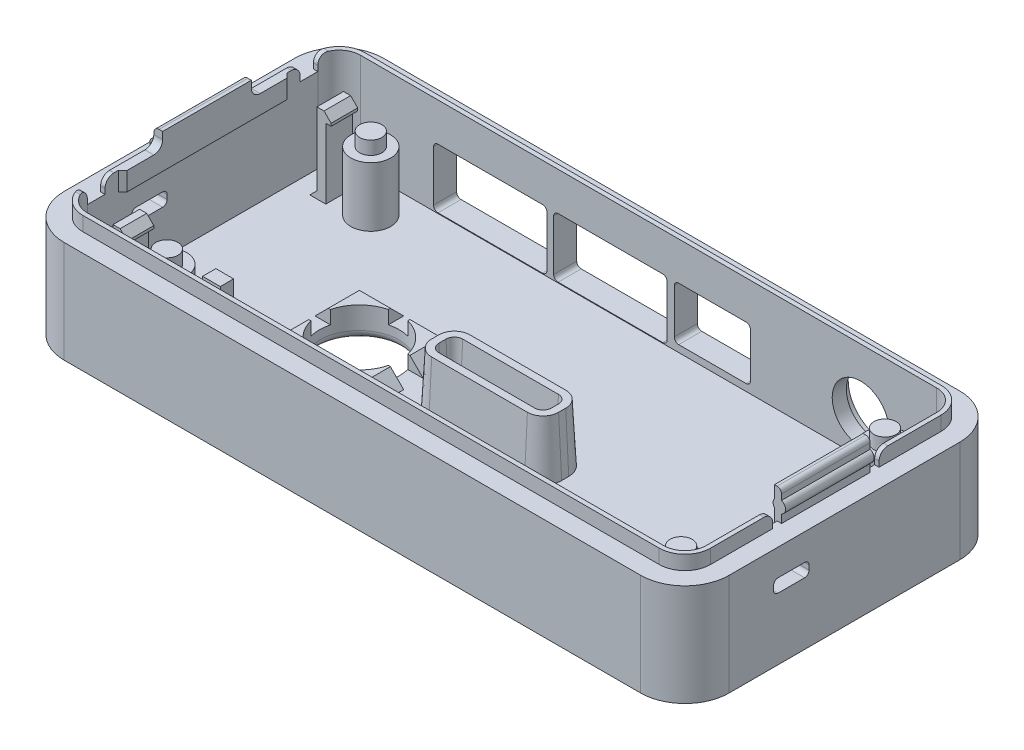
SolidWorks part; units mm, degrees
ref_plane "前视基准面" through (0, 0, 0) normal (0, 0, 1) x (1, 0, 0)
ref_plane "上视基准面" through (0, 0, 0) normal (0, 1, 0) x (1, 0, 0)
ref_plane "右视基准面" through (0, 0, 0) normal (1, 0, 0) x (0, 0, -1)
sketch "zero" plane through (0, 0, 0) normal (0, 1, 0) x (1, 0, 0)
  line L1 (-29.5, 15) -> (29.5, 15)
  line L2 (-32.5, 12) -> (-32.5, -12)
  line L3 (-29.5, -15) -> (29.5, -15)
  line L4 (32.5, 12) -> (32.5, -12)
  line L5 (-32.5, 15) -> (32.5, -15) construction
  line L6 (-32.5, -15) -> (32.5, 15) construction
  line L7 (-25.7, -15) -> (-14.5, -15)
  line L8 (-25.7, -15) -> (-25.7, -9.6569)
  line L9 (-25.7, -9.6569) -> (-14.5, -9.6569)
  line L10 (-14.5, -15) -> (-14.5, -9.6569)
  line L11 (5.2, -15) -> (12.7, -15)
  line L12 (5.2, -15) -> (5.2, -11)
  line L13 (5.2, -11) -> (12.7, -11)
  line L14 (12.7, -15) -> (12.7, -11)
  line L15 (17.8, -15) -> (25.3, -15)
  line L16 (17.8, -15) -> (17.8, -11)
  line L17 (17.8, -11) -> (25.3, -11)
  line L18 (25.3, -15) -> (25.3, -11)
  line L19 (-32.5, 7.7) -> (-19.5, 7.7)
  line L20 (-32.5, 7.7) -> (-32.5, -4.3)
  line L21 (-32.5, -4.3) -> (-19.5, -4.3)
  line L22 (-19.5, 7.7) -> (-19.5, -4.3)
  line L23 (-25.5, 14) -> (25.5, 14)
  line L24 (-25.5, 14) -> (-25.5, 8.8)
  line L25 (-25.5, 8.8) -> (25.5, 8.8)
  line L26 (25.5, 14) -> (25.5, 8.8)
  line L27 (-19.5, 7.2329) -> (-35.5, 7.2329)
  line L28 (-19.5, 7.2329) -> (-19.5, -3.7671)
  line L29 (-19.5, -3.7671) -> (-35.5, -3.7671)
  line L30 (-35.5, 7.2329) -> (-35.5, -3.7671)
  arc A0 (29.5, -15) -> (32.5, -12) centre (29.5, -12) ccw
  arc A1 (29.5, 15) -> (32.5, 12) centre (29.5, 12) cw
  arc A2 (-32.5, -12) -> (-29.5, -15) centre (-29.5, -12) ccw
  arc A3 (-29.5, 15) -> (-32.5, 12) centre (-29.5, 12) ccw
  circle A4 centre (-29, 11.4) radius 3
  circle A5 centre (-29, -11.5) radius 3
  circle A6 centre (29, 11.4) radius 3
  circle A7 centre (29, -11.5) radius 3
  circle A8 centre (-29, 11.4) radius 1.375
  circle A9 centre (-29, -11.5) radius 1.375
  circle A10 centre (29, -11.5) radius 1.375
  circle A11 centre (29, 11.4) radius 1.375
  point P0 (0, 0)
  dimension "D3" = 3
  dimension "D4" = 6
  dimension "D9" = 2.75
  dimension "D1" = 65
  dimension "D2" = 30
  dimension "D5" = 3.6
  dimension "D6" = 3.5
  dimension "D7" = 3.5
  dimension "D8" = 3.5
  dimension "D10" = 12
  dimension "D11" = 7.3
  dimension "D12" = 13
  dimension "D13" = 11.2
  dimension "D14" = 6.8
  dimension "D15" = 19.7
  dimension "D16" = 7.5
  dimension "D17" = 7.5
  dimension "D18" = 5.1
  dimension "D19" = 4
  dimension "D20" = 5.2
  dimension "D21" = 7
  dimension "D22" = 7
  dimension "D23" = 1
  dimension "D24" = 11
  dimension "D25" = 16
sketch "sugar" plane through (0, 0, 0) normal (0, 1, 0) x (1, 0, 0)
  line L1 (-29.5, 15) -> (29.5, 15)
  line L2 (-32.5, 12) -> (-32.5, -12)
  line L3 (-29.5, -15) -> (29.5, -15)
  line L4 (32.5, 12) -> (32.5, -12)
  line L5 (-32.5, 15) -> (32.5, -15) construction
  line L6 (-32.5, -15) -> (32.5, 15) construction
  line L7 (23.5, -11.5) -> (19.5, -11.5)
  line L8 (23.5, -11.5) -> (23.5, -13.9082)
  line L9 (23.5, -13.9082) -> (19.5, -13.9082)
  line L10 (19.5, -11.5) -> (19.5, -13.9082)
  line L11 (16, -11.0071) -> (8.5, -11.0071)
  line L12 (16, -11.0071) -> (16, -15)
  line L13 (16, -15) -> (8.5, -15)
  line L14 (8.5, -11.0071) -> (8.5, -15)
  line L15 (20.5, -13.9082) -> (22.5, -13.9082)
  line L16 (20.5, -13.9082) -> (20.5, -14.8173)
  line L17 (20.5, -14.8173) -> (22.5, -14.8173)
  line L18 (22.5, -13.9082) -> (22.5, -14.8173)
  arc A0 (29.5, 15) -> (32.5, 12) centre (29.5, 12) cw
  arc A1 (29.5, -15) -> (32.5, -12) centre (29.5, -12) ccw
  arc A2 (-32.5, -12) -> (-29.5, -15) centre (-29.5, -12) ccw
  arc A3 (-29.5, 15) -> (-32.5, 12) centre (-29.5, 12) ccw
  circle A4 centre (-29, 11.4) radius 3
  circle A5 centre (-29, 11.4) radius 1.375
  circle A6 centre (-29, -11.5) radius 3
  circle A7 centre (-29, -11.5) radius 1.375
  circle A8 centre (29, 11.4) radius 3
  circle A9 centre (29, 11.4) radius 1.375
  circle A10 centre (29, -11.5) radius 3
  circle A11 centre (29, -11.5) radius 1.375
  dimension "D3" = 3
  dimension "D1" = 65
  dimension "D2" = 30
  dimension "D4" = 9
  dimension "D5" = 4
  dimension "D6" = 3.5
  dimension "D7" = 7.5
  dimension "D8" = 2
  dimension "D9" = 1
sketch "case" plane through (0, 0, 0) normal (0, 1, 0) x (1, 0, 0)
  line L1 (-34.0422, 18) -> (30.9578, 18)
  line L2 (-39.0422, 13) -> (-39.0422, -13)
  line L3 (-34.0422, -18) -> (30.9578, -18)
  line L4 (35.9578, 13) -> (35.9578, -13)
  line L5 (-39.0422, 18) -> (35.9578, -18) construction
  line L6 (-39.0422, -18) -> (35.9578, 18) construction
  arc A0 (-39.0422, -13) -> (-34.0422, -18) centre (-34.0422, -13) ccw
  arc A1 (30.9578, -18) -> (35.9578, -13) centre (30.9578, -13) ccw
  arc A2 (30.9578, 18) -> (35.9578, 13) centre (30.9578, 13) cw
  arc A3 (-34.0422, 18) -> (-39.0422, 13) centre (-34.0422, 13) ccw
  point P0 (-1.5422, 0)
  point P3 (-1.5422, 0)
  dimension "D3" = 5
  dimension "D1" = 75
  dimension "D2" = 36
extrude "凸台-拉伸2" add sketch "case" along normal blind 11.5
sketch "草图2" plane through (0, 0, 0) normal (0, 1, 0) x (1, 0, 0)
  line L4 (-34.0422, -15.4) -> (30.9578, -15.4)
  line L5 (33.3578, -13) -> (33.3578, 13)
  line L6 (30.9578, 15.4) -> (-34.0422, 15.4)
  line L7 (-36.4422, 13) -> (-36.4422, -13)
  line L8 (33.8578, -13) -> (33.8578, 13)
  line L9 (30.9578, 15.9) -> (-34.0422, 15.9)
  line L10 (-36.9422, 13) -> (-36.9422, -13)
  line L11 (-34.0422, -15.9) -> (30.9578, -15.9)
  line L12 (33.8578, -13) -> (33.8578, 13)
  line L13 (30.9578, 15.9) -> (-34.0422, 15.9)
  line L14 (-36.9422, 13) -> (-36.9422, -13)
  line L15 (-34.0422, -15.9) -> (30.9578, -15.9)
  arc A4 (30.9578, -15.4) -> (33.3578, -13) centre (30.9578, -13) ccw
  arc A5 (33.3578, 13) -> (30.9578, 15.4) centre (30.9578, 13) ccw
  arc A6 (-34.0422, 15.4) -> (-36.4422, 13) centre (-34.0422, 13) ccw
  arc A7 (-36.4422, -13) -> (-34.0422, -15.4) centre (-34.0422, -13) ccw
  arc A8 (30.9578, -15.9) -> (33.8578, -13) centre (30.9578, -13) ccw
  arc A9 (33.8578, 13) -> (30.9578, 15.9) centre (30.9578, 13) ccw
  arc A10 (-34.0422, 15.9) -> (-36.9422, 13) centre (-34.0422, 13) ccw
  arc A11 (-36.9422, -13) -> (-34.0422, -15.9) centre (-34.0422, -13) ccw
  arc A12 (30.9578, -15.9) -> (33.8578, -13) centre (30.9578, -13) ccw
  arc A13 (33.8578, 13) -> (30.9578, 15.9) centre (30.9578, 13) ccw
  arc A14 (-34.0422, 15.9) -> (-36.9422, 13) centre (-34.0422, 13) ccw
  arc A15 (-36.9422, -13) -> (-34.0422, -15.9) centre (-34.0422, -13) ccw
  dimension "D1" = 2.1
  dimension "D2" = 0.5
ref_plane "基准面1" through (0, 11.5, 0) normal (0, 1, 0) x (1, 0, 0)
sketch "草图3" plane through (0, 11.5, 0) normal (0, 1, 0) x (1, 0, 0)
  line L4 (-34.0422, -15.4) -> (30.9578, -15.4)
  line L5 (33.3578, -13) -> (33.3578, 13)
  line L6 (30.9578, 15.4) -> (-34.0422, 15.4)
  line L7 (-36.4422, 13) -> (-36.4422, -13)
  line L8 (-34.0422, -15.4) -> (30.9578, -15.4)
  line L9 (33.3578, -13) -> (33.3578, 13)
  line L10 (30.9578, 15.4) -> (-34.0422, 15.4)
  line L11 (-36.4422, 13) -> (-36.4422, -13)
  line L12 (-36.9422, 13) -> (-36.9422, -13)
  line L13 (-34.0422, -15.9) -> (30.9578, -15.9)
  line L14 (33.8578, -13) -> (33.8578, 13)
  line L15 (30.9578, 15.9) -> (-34.0422, 15.9)
  line L16 (-36.9422, 13) -> (-36.9422, -13)
  line L17 (-34.0422, -15.9) -> (30.9578, -15.9)
  line L18 (33.8578, -13) -> (33.8578, 13)
  line L19 (30.9578, 15.9) -> (-34.0422, 15.9)
  arc A4 (30.9578, -15.4) -> (33.3578, -13) centre (30.9578, -13) ccw
  arc A5 (33.3578, 13) -> (30.9578, 15.4) centre (30.9578, 13) ccw
  arc A6 (-34.0422, 15.4) -> (-36.4422, 13) centre (-34.0422, 13) ccw
  arc A7 (-36.4422, -13) -> (-34.0422, -15.4) centre (-34.0422, -13) ccw
  arc A8 (30.9578, -15.4) -> (33.3578, -13) centre (30.9578, -13) ccw
  arc A9 (33.3578, 13) -> (30.9578, 15.4) centre (30.9578, 13) ccw
  arc A10 (-34.0422, 15.4) -> (-36.4422, 13) centre (-34.0422, 13) ccw
  arc A11 (-36.4422, -13) -> (-34.0422, -15.4) centre (-34.0422, -13) ccw
  arc A12 (-36.9422, -13) -> (-34.0422, -15.9) centre (-34.0422, -13) ccw
  arc A13 (30.9578, -15.9) -> (33.8578, -13) centre (30.9578, -13) ccw
  arc A14 (33.8578, 13) -> (30.9578, 15.9) centre (30.9578, 13) ccw
  arc A15 (-34.0422, 15.9) -> (-36.9422, 13) centre (-34.0422, 13) ccw
  arc A16 (-36.9422, -13) -> (-34.0422, -15.9) centre (-34.0422, -13) ccw
  arc A17 (30.9578, -15.9) -> (33.8578, -13) centre (30.9578, -13) ccw
  arc A18 (33.8578, 13) -> (30.9578, 15.9) centre (30.9578, 13) ccw
  arc A19 (-34.0422, 15.9) -> (-36.9422, 13) centre (-34.0422, 13) ccw
  dimension "D1" = 0
  dimension "D2" = 0
extrude "凸台-拉伸4" add sketch "草图3" along normal blind 1.6
sketch "草图5" plane through (0, 11.5, 0) normal (0, 1, 0) x (1, 0, 0)
  line L0 (33.3578, -13) -> (33.3578, 13) construction
  line L1 (33.0578, 5) -> (33.3578, 5)
  line L2 (33.0578, 5) -> (33.0578, -5)
  line L3 (33.0578, -5) -> (33.3578, -5)
  line L4 (33.3578, 5) -> (33.3578, -5)
  line L5 (33.0578, 5) -> (33.3578, -5) construction
  line L6 (33.0578, -5) -> (33.3578, 5) construction
  point P0 (33.2078, 0)
  dimension "D2" = 10
  dimension "D3" = 0.3
  dimension "D4" = 0
ref_plane "基准面3" through (33.8578, 0, 0) normal (1, 0, 0) x (0, 0, -1)
ref_plane "基准面7" through (-36.9422, 0, 0) normal (-1, 0, 0) x (0, 0, 1)
ref_plane "基准面8" through (0, 0, 0) normal (0, -1, 0) x (-1, 0, 0)
sketch "草图14" plane through (0, 11.5, 0) normal (0, 1, 0) x (1, 0, 0)
  line L4 (-34.0422, -15.4) -> (30.9578, -15.4)
  line L5 (33.3578, -13) -> (33.3578, 13)
  line L6 (30.9578, 15.4) -> (-34.0422, 15.4)
  line L7 (-36.4422, 13) -> (-36.4422, -13)
  line L8 (-34.0422, -15.4) -> (30.9578, -15.4)
  line L9 (33.3578, -13) -> (33.3578, 13)
  line L10 (30.9578, 15.4) -> (-34.0422, 15.4)
  line L11 (-36.4422, 13) -> (-36.4422, -13)
  arc A4 (30.9578, -15.4) -> (33.3578, -13) centre (30.9578, -13) ccw
  arc A5 (33.3578, 13) -> (30.9578, 15.4) centre (30.9578, 13) ccw
  arc A6 (-34.0422, 15.4) -> (-36.4422, 13) centre (-34.0422, 13) ccw
  arc A7 (-36.4422, -13) -> (-34.0422, -15.4) centre (-34.0422, -13) ccw
  arc A8 (30.9578, -15.4) -> (33.3578, -13) centre (30.9578, -13) ccw
  arc A9 (33.3578, 13) -> (30.9578, 15.4) centre (30.9578, 13) ccw
  arc A10 (-34.0422, 15.4) -> (-36.4422, 13) centre (-34.0422, 13) ccw
  arc A11 (-36.4422, -13) -> (-34.0422, -15.4) centre (-34.0422, -13) ccw
  dimension "D1" = 0
extrude "切除-拉伸2" cut sketch "草图14" against normal blind 9.5
extrude "凸台-拉伸12" add sketch "草图5" against normal blind 2 and the other way blind 1.6
sketch "草图15" plane through (0, 2, 0) normal (0, 1, 0) x (1, 0, 0)
  line L1 (35.9578, -13) -> (35.9578, 13) construction
  line L5 (-39.0422, 13) -> (-39.0422, -13) construction
  line L6 (-34.0422, -18) -> (30.9578, -18) construction
  line L7 (30.9578, 18) -> (-34.0422, 18) construction
  circle A0 centre (29.0603, -11.5295) radius 2.25
  circle A1 centre (-28.9397, -11.5295) radius 2.25
  circle A2 centre (29.0603, 11.4705) radius 2.25
  circle A3 centre (-28.9397, 11.4705) radius 2.25
  dimension "D1" = 4.5
  dimension "D2" = 6.8975
  dimension "D3" = 10.1025
  dimension "D4" = 6.4705
  dimension "D5" = 6.5295
extrude "凸台-拉伸13" add sketch "草图15" along normal blind 6.7
sketch "草图16" plane through (0, 8.7, 0) normal (0, 1, 0) x (1, 0, 0)
  circle A0 centre (29.0603, -11.5295) radius 1.25
  circle A1 centre (29.0603, 11.4705) radius 1.25
  circle A2 centre (-28.9397, -11.5295) radius 1.25
  circle A3 centre (-28.9397, 11.4705) radius 1.25
  dimension "D1" = 2.5
extrude "凸台-拉伸14" add sketch "草图16" along normal blind 1.5
sketch "草图17" plane through (0, 13.1, 0) normal (0, 1, 0) x (1, 0, 0)
  line L0 (33.3578, -13) -> (33.3578, -5) construction
  line L1 (33.3578, -5) -> (33.8578, -5)
  line L2 (33.3578, -5) -> (33.3578, -6)
  line L3 (33.3578, -6) -> (33.8578, -6)
  line L4 (33.8578, -5) -> (33.8578, -6)
  line L5 (33.3578, -13) -> (33.3578, 13) construction
  line L6 (33.8578, -13) -> (33.8578, 13) construction
  line L8 (33.3578, 5) -> (33.8578, 5)
  line L9 (33.3578, 5) -> (33.3578, 6)
  line L10 (33.3578, 6) -> (33.8578, 6)
  line L11 (33.8578, 5) -> (33.8578, 6)
  dimension "D1" = 1
  dimension "D2" = 1
extrude "切除-拉伸3" cut sketch "草图17" against normal blind 1.6
sketch "草图19" plane through (0, 13.1, 0) normal (0, 1, 0) x (1, 0, 0)
  line L0 (33.0578, 5) -> (33.0578, -5) construction
  line L1 (33.8578, -5) -> (33.0578, -5)
  line L2 (33.8578, -5) -> (33.8578, 5)
  line L3 (33.8578, 5) -> (33.0578, 5)
  line L4 (33.0578, -5) -> (33.0578, 5)
extrude "凸台-拉伸15" add sketch "草图19" along normal blind 1.8
sketch "草图20" plane through (0, 0, -5) normal (0, 0, -1) x (-1, 0, 0)
  line L0 (-30.9578, 11.5) -> (-35.9578, 11.5) construction
  line L3 (-33.8578, 11.5) -> (-33.8578, 14.9) construction
  circle A0 centre (-33.6078, 13.1) radius 0.7
  dimension "D1" = 1.4
  dimension "D2" = 1.6
  dimension "D3" = 0.25
extrude "凸台-拉伸16" add sketch "草图20" against normal blind 10
fillet "圆角4" radius 0.5 1 edges at (33.8578, 14.9, 0)
sketch "草图39" plane through (0, 0, -18) normal (0, 0, -1) x (-1, 0, 0)
  line L0 (-30.9578, 0) -> (34.0422, 0) construction
  line L1 (-35.9578, 11.5) -> (-35.9578, 0) construction
  circle A0 centre (-22.3721, 6.2789) radius 4
  dimension "D1" = 6.2789
  dimension "D3" = 8
  dimension "D2" = 13.5857
extrude "切除-拉伸4" cut sketch "草图39" against normal blind 1
sketch "草图41" plane through (0, 0, -18) normal (0, 0, -1) x (-1, 0, 0)
  line L0 (-30.9578, 0) -> (34.0422, 0) construction
  line L1 (-9.9578, 2.7789) -> (-1.3578, 2.7789)
  line L2 (-9.9578, 2.7789) -> (-9.9578, 8.7789)
  line L3 (-9.9578, 8.7789) -> (-1.3578, 8.7789)
  line L4 (-1.3578, 2.7789) -> (-1.3578, 8.7789)
  line L5 (-0.5578, 2.0789) -> (12.2422, 2.0789)
  line L6 (-0.5578, 2.0789) -> (-0.5578, 8.7789)
  line L7 (-0.5578, 8.7789) -> (12.2422, 8.7789)
  line L8 (12.2422, 2.0789) -> (12.2422, 8.7789)
  line L9 (12.9922, 2.0789) -> (25.7922, 2.0789)
  line L10 (12.9922, 2.0789) -> (12.9922, 8.7789)
  line L11 (12.9922, 8.7789) -> (25.7922, 8.7789)
  line L12 (25.7922, 2.0789) -> (25.7922, 8.7789)
  line L13 (-35.9578, 11.5) -> (-35.9578, 0) construction
  dimension "D1" = 8.7789
  dimension "D2" = 26
  dimension "D3" = 8.6
  dimension "D4" = 6
  dimension "D5" = 0.8
  dimension "D6" = 6.7
  dimension "D7" = 12.8
  dimension "D8" = 0.75
  dimension "D9" = 12.8
extrude "切除-拉伸5" cut sketch "草图41" against normal blind 12
sketch "草图42" plane through (0, 0, -17) normal (0, 0, -1) x (-1, 0, 0)
  circle A0 centre (-22.3721, 6.2789) radius 3.2
  circle A1 centre (-22.3721, 6.2789) radius 4 construction
  point P2 (0, 0)
extrude "切除-拉伸6" cut sketch "草图42" against normal blind 1.6
sketch "草图46" plane through (-36.4422, 0, 0) normal (1, 0, 0) x (0, 0, -1)
  line L0 (13, 13.1) -> (-13, 13.1) construction
  line L1 (-10, 13.1) -> (10, 13.1)
  line L2 (-10, 13.1) -> (-10, 11)
  line L3 (-10, 11) -> (10, 11)
  line L4 (10, 13.1) -> (10, 11)
  line L6 (-18, 11.5) -> (-18, 0) construction
  dimension "D1" = 8
  dimension "D2" = 8
extrude "凸台-拉伸19" add sketch "草图46" along normal blind 0.5
chamfer "倒角3" distance 1 angle 45 2 edges at (-35.9422, 12.05, -10) (-35.9422, 12.05, 10)
sketch "草图48" plane through (0, 13.1, 0) normal (0, 1, 0) x (1, 0, 0)
  line L0 (-35.9422, 9) -> (-35.9422, -9) construction
  line L1 (-35.9422, -5) -> (-36.9422, -5)
  line L2 (-35.9422, -5) -> (-35.9422, 5)
  line L3 (-35.9422, 5) -> (-36.9422, 5)
  line L4 (-36.9422, -5) -> (-36.9422, 5)
  line L5 (-36.9422, 13) -> (-36.9422, -13) construction
extrude "凸台-拉伸21" add sketch "草图48" along normal blind 1.8
sketch "草图49" plane through (0, 0, 5) normal (0, 0, 1) x (1, 0, 0)
  line L0 (-34.0422, 11.5) -> (-39.0422, 11.5) construction
  line L1 (-36.9422, 14.9) -> (-36.9422, 13.1) construction
  circle A0 centre (-36.6922, 13.1) radius 0.7
  dimension "D1" = 1.4
  dimension "D2" = 1.6
  dimension "D3" = 0.25
extrude "凸台-拉伸22" add sketch "草图49" against normal blind 10
sketch "草图50" plane through (0, 13.1, 0) normal (0, 1, 0) x (1, 0, 0)
  line L0 (-36.4422, 13) -> (-36.4422, 9.5) construction
  line L1 (-36.4422, 13) -> (-36.9422, 13)
  line L2 (-36.4422, 13) -> (-36.4422, 11)
  line L3 (-36.4422, 11) -> (-36.9422, 11)
  line L4 (-36.9422, 13) -> (-36.9422, 11)
  line L5 (-36.9422, 13) -> (-36.9422, 5) construction
  line L6 (-36.4422, -9.5) -> (-36.4422, -13) construction
  line L7 (-36.4422, -11) -> (-36.9422, -11)
  line L8 (-36.4422, -11) -> (-36.4422, -13)
  line L9 (-36.4422, -13) -> (-36.9422, -13)
  line L10 (-36.9422, -11) -> (-36.9422, -13)
  line L11 (-36.9422, -5) -> (-36.9422, -13) construction
  line L12 (30.9578, 18) -> (-34.0422, 18) construction
  line L13 (-34.0422, -18) -> (30.9578, -18) construction
  dimension "D1" = 2
  dimension "D2" = 2
  dimension "D3" = 5
  dimension "D4" = 5
extrude "切除-拉伸10" cut sketch "草图50" against normal blind 1.6
fillet "圆角9" radius 1 6 edges at (33.6078, 13.1, 6) (33.6078, 13.1, -6) (-36.6922, 13.1, -13) (-36.6922, 13.1, -11) (-36.6922, 13.1, 11) (-36.6922, 13.1, 13)
fillet "圆角10" radius 0.6 1 edges at (-36.9422, 14.9, 0)
sketch "草图51" plane through (0, 0, 0) normal (0, -1, 0) x (1, 0, 0)
  line L0 (35.9578, 13) -> (35.9578, -13) construction
  line L1 (6.2578, 2.3) -> (-5.7422, 2.3)
  line L2 (6.2578, 2.3) -> (6.2578, 4.3)
  line L3 (6.2578, 4.3) -> (-5.7422, 4.3)
  line L4 (-5.7422, 2.3) -> (-5.7422, 4.3)
  line L5 (30.9578, -18) -> (-34.0422, -18) construction
  dimension "D1" = 2
  dimension "D2" = 12
  dimension "D3" = 29.7
  dimension "D4" = 20.3
extrude "切除-拉伸11" cut sketch "草图51" against normal blind 2
fillet "圆角13" radius 0.6 4 edges at (-5.7422, 1, 4.3) (-5.7422, 1, 2.3) (6.2578, 1, 4.3) (6.2578, 1, 2.3)
sketch "草图52" plane through (0, 2, 0) normal (0, 1, 0) x (1, 0, 0)
  line L0 (-11.5279, -7.2295) -> (-20.7279, -7.2295)
  line L5 (-20.7279, -7.2295) -> (-20.7279, 1.9705)
  line L6 (-11.5279, 1.9705) -> (-20.7279, 1.9705)
  line L7 (-11.5279, -7.2295) -> (-11.5279, 1.9705)
  line L8 (-39.0422, 13) -> (-39.0422, -13) construction
  line L9 (-34.0422, -18) -> (30.9578, -18) construction
  dimension "D1" = 9.2
  dimension "D2" = 9.2
  dimension "D3" = 18.3143
  dimension "D4" = 10.7705
extrude "凸台-拉伸23" add sketch "草图52" along normal blind 1.5
chamfer "倒角5" distance 1.5 angle 45 4 edges at (-16.1279, 2, -1.9705) (-11.5279, 2, 2.6295) (-16.1279, 2, 7.2295) (-20.7279, 2, 2.6295)
sketch "草图53" plane through (0, 0, 0) normal (0, -1, 0) x (1, 0, 0)
  line L1 (30.9578, -18) -> (-34.0422, -18) construction
  line L2 (-39.0422, -13) -> (-39.0422, 13) construction
  circle A0 centre (-16.1279, 2.6295) radius 4.5
  dimension "D1" = 9
  dimension "D2" = 20.6295
  dimension "D3" = 22.9143
extrude "切除-拉伸12" cut sketch "草图53" against normal up to next
fillet "圆角14" radius 1 1 edges at (-16.1279, 0, -1.8705)
sketch "草图55" plane through (0, 3.5, 0) normal (0, 1, 0) x (1, 0, 0)
  line L1 (-10.0279, -3.7295) -> (-22.2279, -3.7295)
  line L2 (-10.0279, -3.7295) -> (-10.0279, -1.5295)
  line L3 (-10.0279, -1.5295) -> (-22.2279, -1.5295)
  line L4 (-22.2279, -3.7295) -> (-22.2279, -1.5295)
  line L5 (-10.0279, -3.7295) -> (-22.2279, -1.5295) construction
  line L6 (-10.0279, -1.5295) -> (-22.2279, -3.7295) construction
  circle A0 centre (-16.1279, -2.6295) radius 4.5 construction
  point P0 (-16.1279, -2.6295)
  dimension "D1" = 12.2
  dimension "D2" = 2.2
extrude "切除-拉伸13" cut sketch "草图55" against normal blind 1.5
sketch "草图56" plane through (0, 3.5, 0) normal (0, 1, 0) x (1, 0, 0)
  line L1 (-15.0279, -8.7295) -> (-17.2279, -8.7295)
  line L2 (-15.0279, -8.7295) -> (-15.0279, 3.4705)
  line L3 (-15.0279, 3.4705) -> (-17.2279, 3.4705)
  line L4 (-17.2279, -8.7295) -> (-17.2279, 3.4705)
  line L5 (-15.0279, -8.7295) -> (-17.2279, 3.4705) construction
  line L6 (-15.0279, 3.4705) -> (-17.2279, -8.7295) construction
  arc A0 (-11.7644, -3.7295) -> (-11.7644, -1.5295) centre (-16.1279, -2.6295) ccw construction
  point P0 (-16.1279, -2.6295)
  dimension "D1" = 12.2
  dimension "D2" = 2.2
extrude "切除-拉伸14" cut sketch "草图56" against normal blind 1.5
sketch "草图62" plane through (0, 0, 0) normal (0, -1, 0) x (1, 0, 0)
  line L54 (31.3299, 13.3324) -> (30.9169, 13.5642)
  line L55 (30.9169, 13.5642) -> (28.7745, 14.7678)
  line L56 (28.7745, 14.7678) -> (28.3615, 15.0024)
  line L57 (27.5011, 14.9926) -> (27.0935, 14.7486)
  line L58 (27.0935, 14.7486) -> (24.9793, 13.4962)
  line L60 (24.9793, 13.4962) -> (24.5717, 13.255)
  line L61 (24.15, 12.5065) -> (24.189, 9.0989)
  line L62 (24.6278, 8.3602) -> (25.0408, 8.1284)
  line L63 (25.0408, 8.1284) -> (27.1831, 6.9248)
  line L65 (27.1831, 6.9248) -> (27.5962, 6.6902)
  line L66 (28.4566, 6.7) -> (28.8641, 6.9441)
  line L67 (28.8641, 6.9441) -> (30.9784, 8.1964)
  line L68 (30.9784, 8.1964) -> (31.3859, 8.4376)
  line L69 (31.8076, 9.1861) -> (31.7686, 12.5937)
  line L70 (25.1226, 12.9222) -> (27.7378, 14.4738)
  line L73 (28.1396, 14.4784) -> (30.7754, 12.9841)
  line L74 (30.7822, 12.6337) -> (28.2554, 11.0831)
  line L75 (29.0741, 8.5137) -> (28.7797, 8.3451)
  line L76 (28.7517, 8.2963) -> (28.7615, 7.4416)
  line L77 (28.7336, 7.3928) -> (28.1845, 7.0731)
  line L78 (28.1013, 7.1205) -> (28.0711, 9.7589)
  line L79 (28.099, 9.8076) -> (29.0331, 10.3512)
  line L80 (31.0237, 8.7127) -> (30.4803, 8.3959)
  line L81 (30.3971, 8.4434) -> (30.3827, 9.6998)
  line L82 (30.4107, 9.7486) -> (30.9541, 10.0626)
  line L83 (31.0373, 10.0151) -> (31.0517, 8.7615)
  line L84 (29.0341, 9.0205) -> (28.7735, 8.8864)
  line L85 (28.7443, 8.9459) -> (28.7366, 9.6183)
  line L86 (28.7646, 9.6671) -> (29.008, 9.8066)
  line L129 (28.7735, 8.8864) -> (28.7797, 8.3451)
  line L130 (28.7443, 8.9459) -> (28.7517, 8.2963)
  spline S0 degree 3 poles (28.3615, 15.0024) (28.2268, 15.075) (28.0782, 15.1132) (27.93, 15.1115) knots 3 3 3 3 4 4 4 4
  spline S1 degree 3 poles (27.93, 15.1115) (27.7818, 15.1098) (27.6341, 15.0682) (27.5011, 14.9926) knots 4 4 4 4 5 5 5 5
  spline S2 degree 3 poles (24.5717, 13.255) (24.3085, 13.0981) (24.1465, 12.8113) (24.15, 12.5065) knots 8 8 8 8 9 9 9 9
  spline S3 degree 3 poles (24.189, 9.0989) (24.1926, 8.7912) (24.3611, 8.511) (24.6278, 8.3602) knots 10 10 10 10 11 11 11 11
  spline S4 degree 3 poles (27.5962, 6.6902) (27.7309, 6.6148) (27.8795, 6.5794) (28.0277, 6.5811) knots 14 14 14 14 15 15 15 15
  spline S5 degree 3 poles (28.0277, 6.5811) (28.1759, 6.5828) (28.3236, 6.6216) (28.4566, 6.7) knots 15 15 15 15 16 16 16 16
  spline S6 degree 3 poles (31.3859, 8.4376) (31.652, 8.5945) (31.8112, 8.8784) (31.8076, 9.1861) knots 19 19 19 19 20 20 20 20
  spline S7 degree 3 poles (31.7686, 12.5937) (31.7651, 12.8986) (31.5995, 13.1816) (31.3299, 13.3324) knots 21 21 21 21 22 22 22 22
  spline S8 degree 2 poles (27.6998, 11.0768) (25.1072, 12.5345) (25.1014, 12.5373) knots 0 0 0 1 1 1
  spline S9 degree 3 poles (25.1014, 12.5373) (24.9664, 12.6326) (24.9783, 12.838) (25.1226, 12.9222) knots 1 1 1 1 2 2 2 2
  spline S10 degree 3 poles (27.7378, 14.4738) (27.8595, 14.5465) (28.0134, 14.5482) (28.1396, 14.4784) knots 3 3 3 3 4 4 4 4
  spline S11 degree 3 poles (30.7754, 12.9841) (30.9101, 12.9087) (30.9152, 12.715) (30.7822, 12.6337) knots 5 5 5 5 6 6 6 6
  spline S12 degree 3 poles (28.2554, 11.0831) (28.0856, 10.9815) (27.8719, 10.979) (27.6998, 11.0768) knots 7 7 7 7 8 8 8 8
  spline S13 degree 3 poles (28.7615, 7.4416) (28.7618, 7.4216) (28.7534, 7.4044) (28.7336, 7.3928) knots 3 3 3 3 4 4 4 4
  spline S14 degree 3 poles (28.1845, 7.0731) (28.1477, 7.0527) (28.1018, 7.0778) (28.1013, 7.1205) knots 5 5 5 5 6 6 6 6
  spline S15 degree 3 poles (28.0711, 9.7589) (28.0708, 9.7788) (28.0792, 9.7988) (28.099, 9.8076) knots 7 7 7 7 8 8 8 8
  spline S16 degree 3 poles (29.0331, 10.3512) (29.6389, 10.7029) (30.1424, 10.7771) (30.1502, 10.0933) knots 9 9 9 9 10 10 10 10
  spline S17 degree 3 poles (30.1502, 10.0933) (30.1577, 9.4351) (29.6544, 8.8509) (29.0741, 8.5137) knots 10 10 10 10 11 11 11 11
  spline S18 degree 3 poles (31.0517, 8.7615) (31.0519, 8.7415) (31.0407, 8.7214) (31.0237, 8.7127) knots 0 0 0 0 1 1 1 1
  spline S19 degree 3 poles (30.4803, 8.3959) (30.4435, 8.3755) (30.3976, 8.4006) (30.3971, 8.4434) knots 2 2 2 2 3 3 3 3
  spline S20 degree 3 poles (30.3827, 9.6998) (30.3825, 9.7198) (30.3937, 9.737) (30.4107, 9.7486) knots 4 4 4 4 5 5 5 5
  spline S21 degree 3 poles (30.9541, 10.0626) (30.991, 10.0829) (31.0368, 10.0578) (31.0373, 10.0151) knots 6 6 6 6 7 7 7 7
  spline S22 degree 3 poles (30.6996, 10.8946) (30.9175, 11.0224) (31.0748, 10.9701) (31.0771, 10.7707) (31.0794, 10.5741) (30.9253, 10.3415) (30.7073, 10.2165) knots 2 2 2 2 3 3 3 4 4 4 4
  spline S23 degree 3 poles (30.7073, 10.2165) (30.4866, 10.0857) (30.3293, 10.1381) (30.327, 10.3346) (30.3247, 10.5369) (30.4788, 10.7667) (30.6996, 10.8946) knots 0 0 0 0 1 1 1 2 2 2 2
  spline S24 degree 3 poles (29.5048, 9.7183) (29.5079, 9.4476) (29.3569, 9.2065) (29.0341, 9.0205) knots 0 0 0 0 1 1 1 1
  spline S25 degree 3 poles (28.7366, 9.6183) (28.7364, 9.6382) (28.7475, 9.6583) (28.7646, 9.6671) knots 4 4 4 4 5 5 5 5
  spline S26 degree 3 poles (29.008, 9.8066) (29.325, 9.9926) (29.5016, 9.9975) (29.5048, 9.7183) knots 6 6 6 6 7 7 7 7
fillet "圆角17" radius 1 2 edges at (-36.4422, 13.1, 5) (-36.4422, 13.1, -5)
sketch "草图63" plane through (0, 2, 0) normal (0, 1, 0) x (1, 0, 0)
  line L0 (30.9578, 15.4) -> (-34.0422, 15.4) construction
  line L1 (-30.4422, -4.5) -> (-28.4422, -4.5)
  line L2 (-30.4422, -4.5) -> (-30.4422, -6)
  line L3 (-30.4422, -6) -> (-28.4422, -6)
  line L4 (-28.4422, -4.5) -> (-28.4422, -6)
  line L5 (-36.4422, 13) -> (-36.4422, -13) construction
  dimension "D1" = 2
  dimension "D2" = 1.5
  dimension "D3" = 19.9
  dimension "D4" = 6
extrude "凸台-拉伸24" add sketch "草图63" along normal blind 2
fillet "圆角18" radius 0.5 12 edges at (1.3578, 8.7789, -16.7) (9.9578, 8.7789, -16.7) (9.9578, 2.7789, -16.7) (1.3578, 2.7789, -16.7) (-12.2422, 2.0789, -16.7) (0.5578, 2.0789, -16.7) (0.5578, 8.7789, -16.7) (-12.2422, 8.7789, -16.7) (-25.7922, 8.7789, -16.7) (-12.9922, 8.7789, -16.7) (-25.7922, 2.0789, -16.7) (-12.9922, 2.0789, -16.7)
sketch "草图66" plane through (0, 2, 0) normal (0, 1, 0) x (1, 0, 0)
  line L8 (-5.1422, -0.8) -> (5.6578, -0.8)
  line L9 (-7.2422, -3.7) -> (-7.2422, -2.9)
  line L10 (5.6578, -5.8) -> (-5.1422, -5.8)
  line L11 (7.7578, -2.9) -> (7.7578, -3.7)
  arc A8 (7.7578, -2.9) -> (5.6578, -0.8) centre (5.6578, -2.9) ccw
  arc A9 (-5.1422, -0.8) -> (-7.2422, -2.9) centre (-5.1422, -2.9) ccw
  arc A10 (-7.2422, -3.7) -> (-5.1422, -5.8) centre (-5.1422, -3.7) ccw
  arc A11 (5.6578, -5.8) -> (7.7578, -3.7) centre (5.6578, -3.7) ccw
extrude "凸台-拉伸27" add sketch "草图66" along normal blind 6.5 draft 3
extrude "切除-拉伸15" cut sketch "草图62" against normal blind 0.5
sketch "草图67" plane through (-39.0422, 0, 0) normal (-1, 0, 0) x (0, 0, 1)
  line L0 (18, 11.5) -> (18, 0) construction
  line L1 (4, 8.5) -> (8, 8.5)
  line L2 (4, 8.5) -> (4, 7)
  line L3 (4, 7) -> (8, 7)
  line L4 (8, 8.5) -> (8, 7)
  line L5 (-13, 11.5) -> (13, 11.5) construction
  dimension "D1" = 4
  dimension "D2" = 1.5
  dimension "D3" = 10
  dimension "D4" = 3
extrude "切除-拉伸16" cut sketch "草图67" against normal up to next
fillet "圆角20" radius 0.5 4 edges at (-37.7422, 7, 8) (-37.7422, 8.5, 8) (-37.7422, 8.5, 4) (-37.7422, 7, 4)
sketch "草图68" plane through (33.3578, 0, 0) normal (-1, 0, 0) x (0, 0, 1)
  line L0 (8, 7.5) -> (8, 8) construction
  line L1 (4.5, 7) -> (7.5, 7) construction
  line L2 (4, 8) -> (4, 7.5) construction
  line L3 (7.5, 8.5) -> (4.5, 8.5) construction
  line L4 (8, 7.5) -> (8, 8)
  line L5 (4.5, 7) -> (7.5, 7)
  line L6 (4, 8) -> (4, 7.5)
  line L7 (7.5, 8.5) -> (4.5, 8.5)
  arc A0 (8, 8) -> (7.5, 8.5) centre (7.5, 8) ccw construction
  arc A1 (7.5, 7) -> (8, 7.5) centre (7.5, 7.5) ccw construction
  arc A2 (4, 7.5) -> (4.5, 7) centre (4.5, 7.5) ccw construction
  arc A3 (4.5, 8.5) -> (4, 8) centre (4.5, 8) ccw construction
  arc A4 (8, 8) -> (7.5, 8.5) centre (7.5, 8) ccw
  arc A5 (7.5, 7) -> (8, 7.5) centre (7.5, 7.5) ccw
  arc A6 (4, 7.5) -> (4.5, 7) centre (4.5, 7.5) ccw
  arc A7 (4.5, 8.5) -> (4, 8) centre (4.5, 8) ccw
extrude "切除-拉伸17" cut sketch "草图68" against normal up to next
sketch "草图70" plane through (0, 2, 0) normal (0, -1, 0) x (1, 0, 0)
  line L0 (5.6578, 4.3) -> (-5.1422, 4.3) construction
  line L1 (-5.7422, 3.7) -> (-5.7422, 2.9) construction
  line L2 (-5.1422, 2.3) -> (5.6578, 2.3) construction
  line L3 (6.2578, 2.9) -> (6.2578, 3.7) construction
  line L4 (6.2578, 2.9) -> (6.2578, 3.7)
  line L5 (-5.1422, 2.3) -> (5.6578, 2.3)
  line L6 (-5.7422, 3.7) -> (-5.7422, 2.9)
  line L7 (5.6578, 4.3) -> (-5.1422, 4.3)
  arc A0 (6.2578, 3.7) -> (5.6578, 4.3) centre (5.6578, 3.7) ccw construction
  arc A1 (-5.1422, 4.3) -> (-5.7422, 3.7) centre (-5.1422, 3.7) ccw construction
  arc A2 (-5.7422, 2.9) -> (-5.1422, 2.3) centre (-5.1422, 2.9) ccw construction
  arc A3 (5.6578, 2.3) -> (6.2578, 2.9) centre (5.6578, 2.9) ccw construction
  arc A4 (6.2578, 3.7) -> (5.6578, 4.3) centre (5.6578, 3.7) ccw
  arc A5 (5.6578, 2.3) -> (6.2578, 2.9) centre (5.6578, 2.9) ccw
  arc A6 (-5.7422, 2.9) -> (-5.1422, 2.3) centre (-5.1422, 2.9) ccw
  arc A7 (-5.1422, 4.3) -> (-5.7422, 3.7) centre (-5.1422, 3.7) ccw
  point P3 (6.0821, 4.1243)
extrude "切除-拉伸18" cut sketch "草图70" against normal up to next (6.5 mm away) draft 3 draft outward yes
sketch "草图71" plane through (33.3578, 0, 0) normal (-1, 0, 0) x (0, 0, 1)
  line L0 (13, 2) -> (-13, 2) construction
  line L1 (-9, 11) -> (-7, 11)
  line L2 (-9, 11) -> (-9, 10)
  line L3 (-9, 10) -> (-7, 10)
  line L4 (-7, 11) -> (-7, 10)
  line L5 (7, 11) -> (9, 11)
  line L6 (7, 11) -> (7, 10)
  line L7 (7, 10) -> (9, 10)
  line L8 (9, 11) -> (9, 10)
  line L10 (-18, 11.5) -> (-18, 0) construction
  line L11 (18, 11.5) -> (18, 0) construction
  point P10 (0, 0)
  dimension "D1" = 2
  dimension "D2" = 2
  dimension "D3" = 1
  dimension "D4" = 8
  dimension "D5" = 9
  dimension "D6" = 9
extrude "凸台-拉伸28" add sketch "草图71" along normal blind 1.2
chamfer "倒角6" distance 0.8 angle 45 2 edges at (32.1578, 11, 8) (32.1578, 11, -8)
sketch "草图73" plane through (0, 2, 0) normal (0, 1, 0) x (1, 0, 0)
  line L0 (30.9578, 18) -> (-34.0422, 18) construction
  line L1 (-33.5422, 13) -> (-32.5422, 13)
  line L2 (-33.5422, 13) -> (-33.5422, 10)
  line L3 (-33.5422, 10) -> (-32.5422, 10)
  line L4 (-32.5422, 13) -> (-32.5422, 10)
  line L5 (-33.5422, -10) -> (-32.5422, -10)
  line L6 (-33.5422, -10) -> (-33.5422, -13)
  line L7 (-33.5422, -13) -> (-32.5422, -13)
  line L8 (-32.5422, -10) -> (-32.5422, -13)
  line L9 (-34.0422, -18) -> (30.9578, -18) construction
  line L10 (-39.0422, 13) -> (-39.0422, -13) construction
  dimension "D1" = 5
  dimension "D2" = 3
  dimension "D3" = 3
  dimension "D4" = 5
  dimension "D5" = 1
  dimension "D6" = 1
  dimension "D7" = 5.5
  dimension "D8" = 5.5
extrude "凸台-拉伸30" add sketch "草图73" along normal blind 9
sketch "草图74" plane through (-32.5422, 0, 0) normal (1, 0, 0) x (0, 0, -1)
  line L0 (10, 11) -> (10, 2) construction
  line L1 (10, 11) -> (13, 11)
  line L2 (10, 11) -> (10, 9.9)
  line L3 (10, 9.9) -> (13, 9.9)
  line L4 (13, 11) -> (13, 9.9)
  line L5 (10, 11) -> (13, 11) construction
  line L6 (13, 11) -> (13, 2) construction
  line L7 (-13, 11) -> (-10, 11) construction
  line L8 (-13, 11) -> (-10, 11)
  line L9 (-13, 11) -> (-13, 9.9)
  line L10 (-13, 9.9) -> (-10, 9.9)
  line L11 (-10, 11) -> (-10, 9.9)
  line L12 (-10, 11) -> (-10, 2) construction
  dimension "D1" = 1.1
  dimension "D2" = 1.1
extrude "凸台-拉伸31" add sketch "草图74" along normal blind 0.6
chamfer "倒角7" distance 0.8 angle 45 4 edges at (-33.5422, 2, 11.5) (-33.5422, 2, -11.5) (-31.9422, 11, 11.5) (-31.9422, 11, -11.5)
